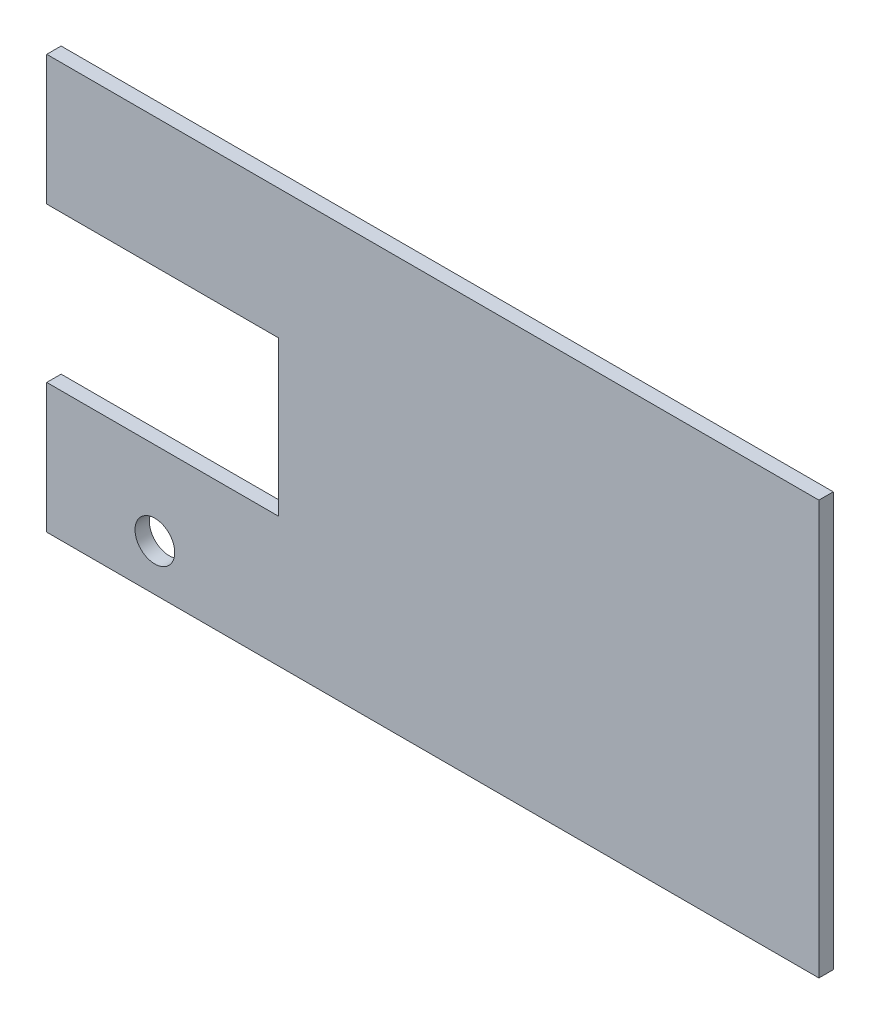
SolidWorks part; units mm, degrees
ref_plane "Front Plane" through (0, 0, 0) normal (0, 0, 1) x (1, 0, 0)
ref_plane "Top Plane" through (0, 0, 0) normal (0, 1, 0) x (1, 0, 0)
ref_plane "Right Plane" through (0, 0, 0) normal (1, 0, 0) x (0, 0, -1)
sketch "Sketch1" plane through (0, 0, 0) normal (0, 0, 1) x (1, 0, 0)
  line L1 (0, 0) -> (127, 0)
  line L2 (0, 0) -> (0, 68.072)
  line L3 (0, 68.072) -> (127, 68.072)
  line L4 (127, 0) -> (127, 68.072)
  dimension "D1" = 68.072
  dimension "D2" = 127
extrude "Boss-Extrude1" add sketch "Sketch1" along normal blind 2.3622
sketch "Sketch2" plane through (0, 0, 2.3622) normal (0, 0, 1) x (1, 0, 0)
  line L0 (0, 68.072) -> (0, 0) construction
  line L1 (0, 46.736) -> (38.1, 46.736)
  line L2 (0, 46.736) -> (0, 21.336)
  line L3 (0, 21.336) -> (38.1, 21.336)
  line L4 (38.1, 46.736) -> (38.1, 21.336)
  line L5 (127, 0) -> (127, 68.072) construction
  point P6 (38.1, 34.036)
  point P7 (127, 34.036)
  dimension "D1" = 25.4
  dimension "D2" = 38.1
extrude "Cut-Extrude1" cut sketch "Sketch2" against normal through all
sketch "Sketch3" plane through (0, 0, 2.3622) normal (0, 0, 1) x (1, 0, 0)
  line L0 (0, 0) -> (127, 0) construction
  line L1 (0, 21.336) -> (0, 0) construction
  circle A0 centre (17.78, 7.62) radius 3.2639
  dimension "D3" = 6.5278
  dimension "D1" = 7.62
  dimension "D2" = 17.78
extrude "Cut-Extrude2" cut sketch "Sketch3" against normal through all
